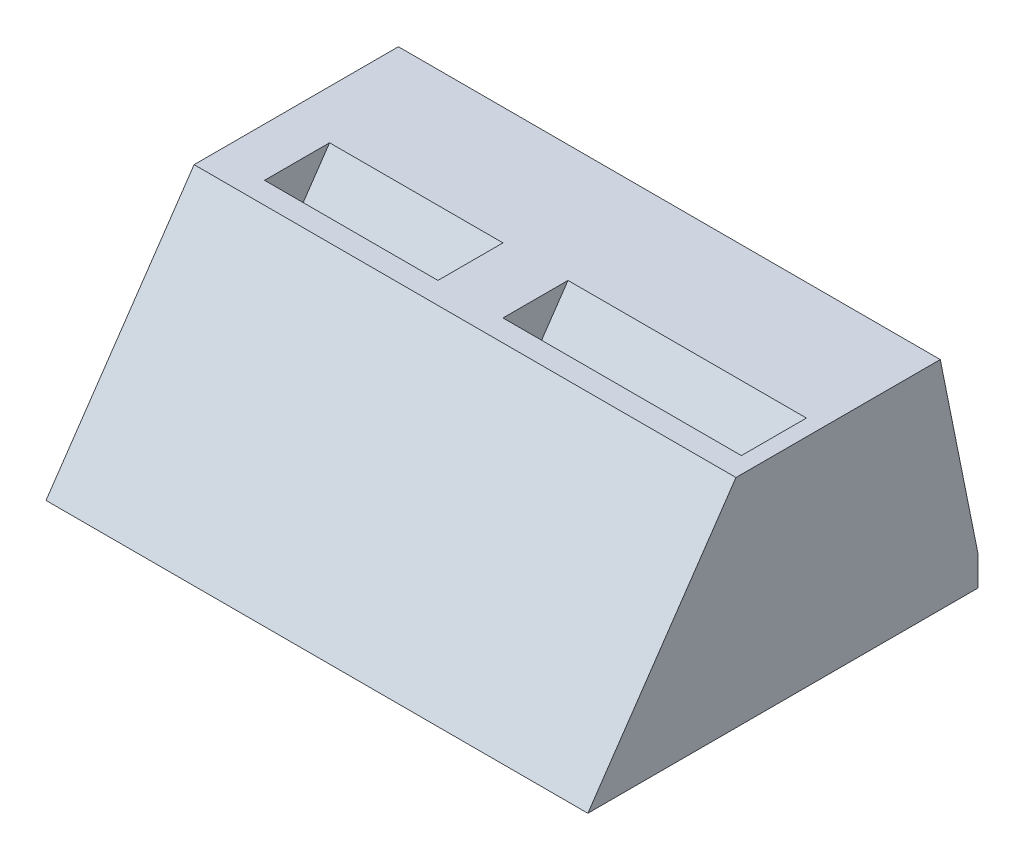
SolidWorks part; units mm, degrees
ref_plane "Ebene vorne" through (0, 0, 0) normal (0, 0, 1) x (1, 0, 0)
ref_plane "Ebene oben" through (0, 0, 0) normal (0, 1, 0) x (1, 0, 0)
ref_plane "Ebene rechts" through (0, 0, 0) normal (1, 0, 0) x (0, 0, -1)
sketch "Skizze1" plane through (0, 0, 0) normal (0, 0, 1) x (1, 0, 0)
  line L1 (-25, -15) -> (25, -15)
  line L2 (-25, -15) -> (-25, 15)
  line L3 (-25, 15) -> (25, 15)
  line L4 (25, -15) -> (25, 15)
  line L5 (-25, -15) -> (25, 15) construction
  line L6 (-25, 15) -> (25, -15) construction
  point P0 (0, 0)
  dimension "D1" = 50
  dimension "D2" = 30
extrude "Aufsatz-Linear austragen1" add sketch "Skizze1" along normal blind 40
ref_plane "Ebene1" through (0, 0, 0) normal (-1, 0, 0) x (0, 0, 1)
sketch "Skizze2" plane through (0, 0, 0) normal (-1, 0, 0) x (0, 0, 1)
  line L0 (7.5, 15) -> (28, -15)
  line L1 (40, 15) -> (0, 15) construction
  line L2 (40, -15) -> (0, -15) construction
  line L3 (28, -15) -> (34, -15)
  line L4 (34, -15) -> (13.5, 15)
  line L5 (13.5, 15) -> (7.5, 15)
  line L6 (40, 15) -> (40, -15) construction
  line L8 (26.6333, -13) -> (32.6333, -13)
  dimension "D1" = 6
  dimension "D2" = 6
  dimension "D3" = 7.5
  dimension "D4" = 2
extrude "FPV_Sender" cut sketch "Skizze2" against normal blind 22 from offset 1.5 contours L0 L8 L4 L5 region at (0, 1, 20.0667) offset against normal yes
sketch "Skizze4" plane through (0, 0, 0) normal (-1, 0, 0) x (0, 0, 1)
  line L0 (13.5, 15) -> (7.5, 15)
  line L1 (7.5, 15) -> (26.6333, -13)
  line L2 (7.5, 15) -> (26.6333, -13) construction
  line L3 (26.6333, -13) -> (32.6333, -13)
  line L4 (32.6333, -13) -> (13.5, 15) construction
  line L5 (32.6333, -13) -> (13.5, 15)
  dimension "D1" = 28
extrude "Empfänger" cut sketch "Skizze4" along normal blind 16 from offset 4.5
sketch "Skizze5" plane through (-25, 0, 0) normal (-1, 0, 0) x (0, 0, 1)
  line L0 (15.5, 15) -> (40, 15)
  line L1 (40, 15) -> (0, 15) construction
  line L2 (40, 15) -> (40, -20.8537)
  line L3 (40, 15) -> (40, -15) construction
  line L4 (40, -20.8537) -> (15.5, 15)
  line L5 (32.6333, -13) -> (13.5, 15) construction
  line L6 (5.5, 15) -> (0, -12.25)
  line L7 (0, 15) -> (0, -15) construction
  line L8 (0, -12.25) -> (0, 15)
  line L9 (0, 15) -> (5.5, 15)
  line L10 (40, -15) -> (0, -15) construction
  dimension "D1" = 2
  dimension "D2" = 2.75
  dimension "D3" = 2
extrude "Schnitt-Linear austragen3" cut sketch "Skizze5" against normal through all and the other way through all
sketch "Skizze7" plane through (25, 0, 0) normal (1, 0, 0) x (0, 0, -1)
  line L0 (-5.5, 15) -> (-15.5, 15)
  line L1 (-15.5, 15) -> (-22.3333, 5)
  line L2 (-15.5, 15) -> (-36, -15) construction
  line L3 (-22.3333, 5) -> (-3.4817, 5)
  line L4 (0, -12.25) -> (-5.5, 15) construction
  line L5 (-3.4817, 5) -> (-5.5, 15)
  dimension "D1" = 10
extrude "Schnitt-Linear austragen5" cut sketch "Skizze7" against normal up to surface (50 mm away) up to face at (-25, 0.55, 11.95)
shell "Wandung2" thickness 2 removed face at (0, -15, 18)
sketch "Skizze6" plane through (0, -13, 0) normal (0, 1, 0) x (1, 0, 0)
  line L0 (23.5, -26.6333) -> (1.5, -26.6333) construction
  line L1 (1.5, -32.6333) -> (8.5, -32.6333)
  line L2 (1.5, -32.6333) -> (1.5, -26.6333)
  line L3 (1.5, -26.6333) -> (8.5, -26.6333)
  line L4 (8.5, -32.6333) -> (8.5, -26.6333)
  dimension "D1" = 7
extrude "Schnitt-Linear austragen4" cut sketch "Skizze6" against normal up to surface (2 mm away) up to face at (-5.1, -15, 24.0621)
sketch "Skizze8" plane through (0, -13, 0) normal (0, 1, 0) x (1, 0, 0)
  line L0 (-20.5, -26.6333) -> (-4.5, -26.6333) construction
  line L1 (-4.5, -32.6333) -> (-8.5, -32.6333)
  line L2 (-4.5, -32.6333) -> (-4.5, -26.6333)
  line L3 (-4.5, -26.6333) -> (-8.5, -26.6333)
  line L4 (-8.5, -32.6333) -> (-8.5, -26.6333)
  dimension "D1" = 4
extrude "Schnitt-Linear austragen7" cut sketch "Skizze8" against normal up to surface (2 mm away) up to face at (5, -15, 29.6333)
